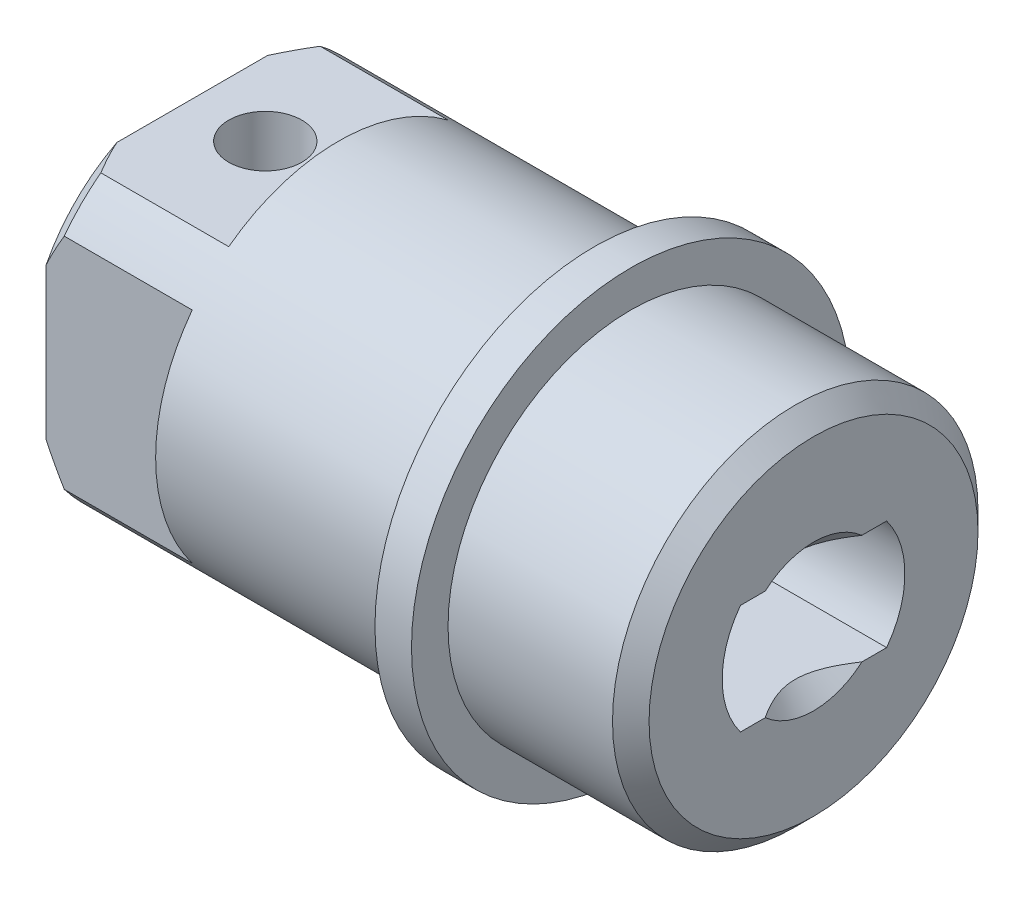
SolidWorks part; units mm, degrees
material "6061-T6 (GB)"
ref_plane "前视" through (0, 0, 0) normal (0, 0, 1) x (1, 0, 0)
ref_plane "上视" through (0, 0, 0) normal (0, 1, 0) x (1, 0, 0)
ref_plane "右视" through (0, 0, 0) normal (1, 0, 0) x (0, 0, -1)
sketch "草图1" plane through (0, 0, 0) normal (0, 0, 1) x (1, 0, 0)
  line L0 (0, 0) -> (44.0136, 0) construction
  line L1 (0, 0) -> (0, 5)
  line L2 (0, 5) -> (11, 5)
  line L3 (11, 5) -> (11, 6)
  line L4 (11, 6) -> (12, 6)
  line L5 (12, 6) -> (12, 5)
  line L6 (12, 5) -> (17, 5)
  line L7 (17, 5) -> (17, 1.5)
  line L8 (17, 1.5) -> (7, 1.5)
  line L9 (7, 1.5) -> (6.134, 0)
  line L10 (6.134, 0) -> (0, 0)
  point P3 (11.4256, 6.7927)
  dimension "D1" = 10
  dimension "D2" = 3
  dimension "D3" = 1
  dimension "D4" = 12
  dimension "D5" = 5
  dimension "D6" = 11
  dimension "D7" = 60
  dimension "D8" = 10
revolve "旋转1" add sketch "草图1" angle 360 about L0
chamfer "倒角1" distance 0.5 angle 45 3 edges at (17, 0, 1.5) (17, 0, 5) (0, 0, 5)
sketch "草图2" plane through (0, 0, 0) normal (-1, 0, 0) x (0, 0, 1)
  line L1 (-4, -4) -> (4, -4)
  line L2 (-4, -4) -> (-4, 4)
  line L3 (-4, 4) -> (4, 4)
  line L4 (4, -4) -> (4, 4)
  line L5 (-4, -4) -> (4, 4) construction
  line L6 (-4, 4) -> (4, -4) construction
  point P0 (0, 0)
  dimension "D1" = 8
extrude "切除-拉伸1" cut sketch "草图2" against normal blind 4 flip side to cut
sketch "草图3" plane through (0, 0, 0) normal (0, 1, 0) x (1, 0, 0)
  line L0 (0, 0) -> (6.4434, 0) construction
  line L2 (0, 4) -> (0, 2.0616) construction
  circle A0 centre (2, 0) radius 1
  dimension "D1" = 2
  dimension "D2" = 2
extrude "切除-拉伸2" cut sketch "草图3" against normal mid plane 24
sketch "草图4" plane through (17, 0, 0) normal (1, 0, 0) x (0, 0, -1)
  line L0 (-7.1097, 0) -> (7.4297, 0) construction
  line L1 (-2, 1.5) -> (2, 1.5)
  line L2 (-2, -1.5) -> (2, -1.5)
  arc A0 (-2, 1.5) -> (-2, -1.5) centre (0, 0) ccw
  arc A1 (2, -1.5) -> (2, 1.5) centre (0, 0) ccw
  point P7 (-1.8534, -1.6778)
  dimension "D1" = 2.5
  dimension "D2" = 3
extrude "切除-拉伸3" cut sketch "草图4" against normal blind 10
